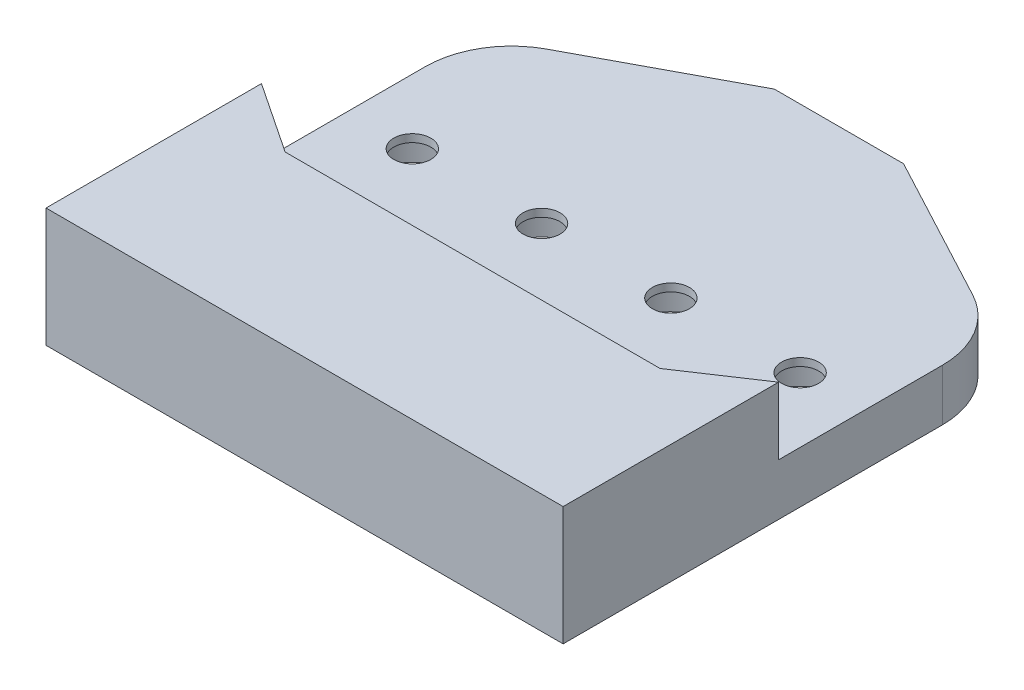
SolidWorks part; units mm, degrees
ref_plane "Front Plane" through (0, 0, 0) normal (0, 0, 1) x (1, 0, 0)
ref_plane "Top Plane" through (0, 0, 0) normal (0, 1, 0) x (1, 0, 0)
ref_plane "Right Plane" through (0, 0, 0) normal (1, 0, 0) x (0, 0, -1)
sketch "Sketch2" plane through (0, 0, 0) normal (0, 1, 0) x (1, 0, 0)
  line L0 (0, 0) -> (0, 35)
  line L1 (0, 35) -> (22.5, 47)
  line L2 (22.5, 47) -> (37.5, 47)
  line L3 (37.5, 47) -> (60, 35)
  line L4 (60, 35) -> (60, 0)
  line L5 (60, 0) -> (0, 0)
  line L6 (22.5, 20) -> (37.5, 20) construction
  line L7 (30, 47) -> (30, 0) construction
  circle A0 centre (7.5, 20) radius 2.15
  circle A1 centre (22.5, 20) radius 2.15
  circle A2 centre (37.5, 20) radius 2.15
  circle A3 centre (52.5, 20) radius 2.15
  point P17 (30, 20)
  dimension "D5" = 4.3
  dimension "D7" = 15
  dimension "D8" = 15
  dimension "D9" = 15
  dimension "D6" = 20
  dimension "D1" = 60
  dimension "D2" = 35
  dimension "D3" = 15
  dimension "D4" = 12
extrude "Boss-Extrude1" add sketch "Sketch2" along normal blind 6
sketch "Sketch3" plane through (0, 6, 0) normal (0, 1, 0) x (1, 0, 0)
  line L0 (0, 0) -> (0, 10)
  line L1 (0, 35) -> (0, 0) construction
  line L2 (0, 10) -> (15, 0)
  line L3 (0, 0) -> (60, 0) construction
  line L4 (15, 0) -> (0, 0)
  line L5 (60, 0) -> (60, 10)
  line L6 (60, 0) -> (60, 35) construction
  line L7 (60, 10) -> (45, 0)
  line L8 (45, 0) -> (60, 0)
  line L9 (51.75, 4.5) -> (8.25, 4.5)
  line M8 (0, 0) -> (60, 0)
  line M9 (60, 0) -> (60, 35)
  line M13 (0, 35) -> (0, 0)
  dimension "D1" = 15
  dimension "D2" = 10
  dimension "D3" = 4.5
extrude "Boss-Extrude2" add sketch "Sketch3" along normal blind 7.8 contours L2 M13 M8 | L7 L9 L2 M8 | L7 M9 M8 region at (5, 6, -3.3333) region at (30, 6, -2.3878) region at (55, 6, -3.3333)
sketch "Sketch4" plane through (0, 13.8, 0) normal (0, 1, 0) x (1, 0, 0)
  line L0 (0, 0) -> (60, 0) construction
  line L1 (0, 10) -> (0, 0) construction
  line L2 (60, 0) -> (60, 10) construction
  circle A0 centre (3, 4.25) radius 1.7
  circle A1 centre (57, 4.25) radius 1.7
  dimension "D1" = 3.4
  dimension "D2" = 4.25
  dimension "D3" = 3
  dimension "D4" = 3
extrude "Cut-Extrude1" [suppressed] cut sketch "Sketch4" against normal through all
sketch "Sketch5" plane through (0, 0, 0) normal (0, 1, 0) x (1, 0, 0)
  circle A0 centre (7.5, 20) radius 6.55
  circle A1 centre (22.5, 20) radius 6.55
  circle A2 centre (37.5, 20) radius 6.55
  circle A3 centre (52.5, 20) radius 6.55
  dimension "D1" = 13.1
extrude "Cut-Extrude2" cut sketch "Sketch5" along normal blind 5.1
fillet "Fillet1" radius 10 2 edges at (0, 3, -35) (60, 3, -35)
sketch "Sketch6" [suppressed] plane through (0, 0, 0) normal (0, -1, 0) x (-1, 0, 0)
  line L0 (-25, 42.25) -> (-35, 42.25) construction
  line L1 (-37.5, 47) -> (-22.5, 47) construction
  line L2 (-3, 4.25) -> (-25, 4.25) construction
  circle A0 centre (-25, 42.25) radius 2.6
  circle A1 centre (-35, 42.25) radius 2.6
  circle A2 centre (-35, 4.25) radius 2.6
  circle A3 centre (-25, 4.25) radius 2.6
  point P10 (-30, 47)
  point P11 (-30, 42.25)
  dimension "D1" = 5.2
  dimension "D2" = 10
  dimension "D3" = 38
extrude "Cut-Extrude3" [suppressed] cut sketch "Sketch6" against normal blind 5
sketch "Sketch7" plane through (0, 0, 0) normal (0, 0, 1) x (1, 0, 0)
  line L1 (0, 13.8) -> (60, 13.8)
  line L2 (0, 13.8) -> (0, 0)
  line L3 (0, 0) -> (60, 0)
  line L4 (60, 13.8) -> (60, 0)
extrude "Boss-Extrude3" add sketch "Sketch7" along normal blind 15
